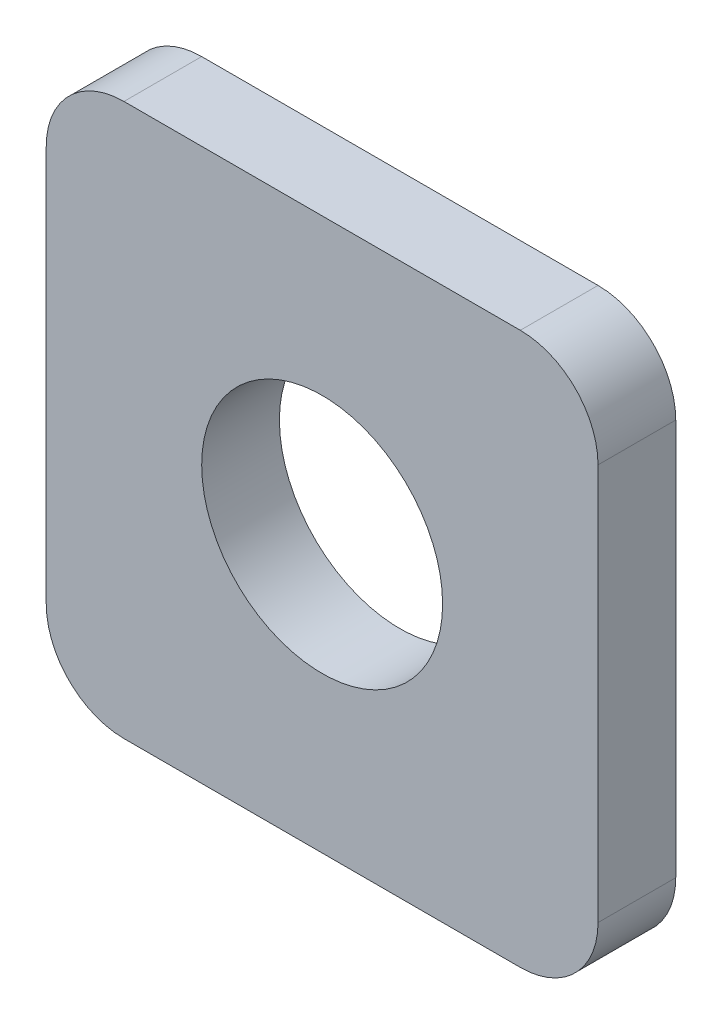
SolidWorks part; units mm, degrees
material "1.4003 (X2CrNi12)"
ref_plane "Ön Düzlem" through (0, 0, 0) normal (0, 0, 1) x (1, 0, 0)
ref_plane "Üst Düzlem" through (0, 0, 0) normal (0, 1, 0) x (1, 0, 0)
ref_plane "Sağ Düzlem" through (0, 0, 0) normal (1, 0, 0) x (0, 0, -1)
sketch "Çizim1" plane through (0, 0, 0) normal (0, 0, 1) x (1, 0, 0)
  line L1 (-35.5, 35.5) -> (35.5, 35.5)
  line L2 (-35.5, 35.5) -> (-35.5, -35.5)
  line L3 (-35.5, -35.5) -> (35.5, -35.5)
  line L4 (35.5, 35.5) -> (35.5, -35.5)
  line L5 (-35.5, 35.5) -> (35.5, -35.5) construction
  line L6 (-35.5, -35.5) -> (35.5, 35.5) construction
  circle A0 centre (0, 0) radius 15.5
  point P0 (0, 0)
  dimension "D3" = 31
  dimension "D1" = 71
  dimension "D2" = 71
base flange "Taban-Flanş1" sketch "Çizim1" thickness 10 reverse thickness direction no parameters "D1"=5
fillet "Radyus1" radius 10 4 edges at (-35.5, 35.5, -5) (35.5, 35.5, -5) (35.5, -35.5, -5) (-35.5, -35.5, -5)
sketch "Büküm-Çizgileri1" [suppressed] plane through (0, 0, 0) normal (0, 1, 0) x (1, 0, 0)
sketch "Sınırlandırma-Kutusu1" [suppressed] plane through (0, 0, 0) normal (0, 1, 0) x (1, 0, 0)
sheet metal parameters "Sac-Levha1" thickness 10 parameters "D1"=5
flat pattern "Düz-Çoğaltma1" [suppressed]
sketch "Büküm-Çizgileri2" plane through (0, 0, 0) normal (0, 1, 0) x (1, 0, 0)
sketch3d "Sınırlandırma-Kutusu2" [suppressed]
  line L0 (-35.5, -35.5, 0) -> (35.5, -35.5, 0) construction
  line L1 (-35.5, 35.5, 0) -> (35.5, 35.5, 0) construction
  line L2 (-35.5, -35.5, 0) -> (-35.5, 35.5, 0) construction
  line L3 (35.5, -35.5, 0) -> (35.5, 35.5, 0) construction
